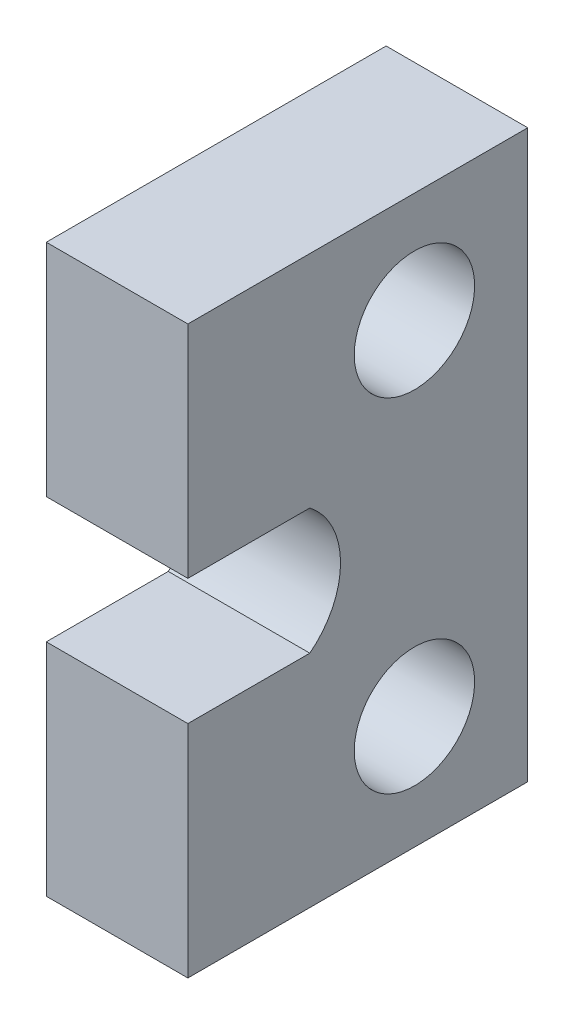
SolidWorks part; units mm, degrees
material "Plain Carbon Steel"
ref_plane "Front Plane" through (0, 0, 0) normal (0, 0, 1) x (1, 0, 0)
ref_plane "Top Plane" through (0, 0, 0) normal (0, 1, 0) x (1, 0, 0)
ref_plane "Right Plane" through (0, 0, 0) normal (1, 0, 0) x (0, 0, -1)
sketch "Sketch1" plane through (0, 0, 0) normal (0, 0, 1) x (1, 0, 0)
  line L1 (0, 0) -> (15.875, 0)
  line L2 (0, 0) -> (0, 63.5)
  line L3 (0, 63.5) -> (15.875, 63.5)
  line L4 (15.875, 0) -> (15.875, 63.5)
  dimension "D1" = 63.5
  dimension "D2" = 15.875
extrude "Boss-Extrude1" add sketch "Sketch1" along normal blind 38.1
sketch "Sketch2" plane through (0, 0, 0) normal (-1, 0, 0) x (0, 0, 1)
  line L0 (0, 31.75) -> (31.75, 31.75)
  line L1 (37.2412, 38.7985) -> (24.428, 38.7985)
  line L2 (24.428, 24.7015) -> (37.2412, 24.7015)
  line L3 (30.8346, 38.7985) -> (30.8346, 24.7015)
  line L4 (24.428, 38.7985) -> (0, 38.7985)
  line L5 (24.428, 24.7015) -> (0, 24.7015)
  line L6 (0, 63.5) -> (0, 0) construction
  line L7 (38.1, 63.5) -> (38.1, 0) construction
  line L8 (37.2412, 38.7985) -> (38.1, 38.7985)
  line L9 (37.2412, 38.7985) -> (37.2412, 24.7015)
  line L10 (37.2412, 24.7015) -> (38.1, 24.7015)
  line L11 (38.1, 38.7985) -> (38.1, 24.7015)
  arc A0 (37.2412, 38.7985) -> (37.2412, 24.7015) centre (31.75, 31.75) cw
  arc A1 (24.428, 38.7985) -> (24.428, 24.7015) centre (29.9192, 31.75) ccw
  point P10 (40.685, 31.75)
  point P17 (0, 31.75)
  dimension "D1" = 31.75
  dimension "D2" = 12.8132
  dimension "D3" = 12.8132
  dimension "D4" = 14.097
  dimension "D5" = 8.935
extrude "Cut-Extrude1" cut sketch "Sketch2" against normal through all contours L1 A1 L0 L3 | L0 A1 L2 L3 | L9 L1 L3 L2 | A0 L11 L9 | A0 L11 | L9 L8 L11 L10 | A1 L2 A0 L1 region at (0, 35.057, 26.3751) region at (0, 28.443, 26.3751) region at (0, 31.75, 34.0379) region at (0, 31.75, 37.6624) region at (0, 31.75, 39.148)
sketch "Sketch3" plane through (0, 0, 0) normal (-1, 0, 0) x (0, 0, 1)
  line L0 (12.7, 0) -> (12.7, 12.7)
  line L2 (12.7, 63.8492) -> (12.7, 51.1493)
  line L4 (0, 51.1493) -> (12.7, 51.1493)
  line L5 (0, 63.5) -> (0, 0) construction
  circle A0 centre (12.7, 51.1493) radius 6.7469
  circle A1 centre (12.7, 12.7) radius 6.7469
  dimension "D3" = 13.4937
  dimension "D4" = 13.4937
  dimension "D1" = 12.7
  dimension "D2" = 12.7
  dimension "D5" = 12.7
extrude "Cut-Extrude2" cut sketch "Sketch3" against normal through all contours A0 | A1 | A0 region at (0, 50.1948, 13.6545) region at (0, 8.0642, 17.3358)
equation "\"D2@Sketch3\"=\"D1@Sketch3\""
equation "\"D4@Sketch3\"=\"D3@Sketch3\""
equation "\"D5@Sketch3\"=\"D1@Sketch3\""
